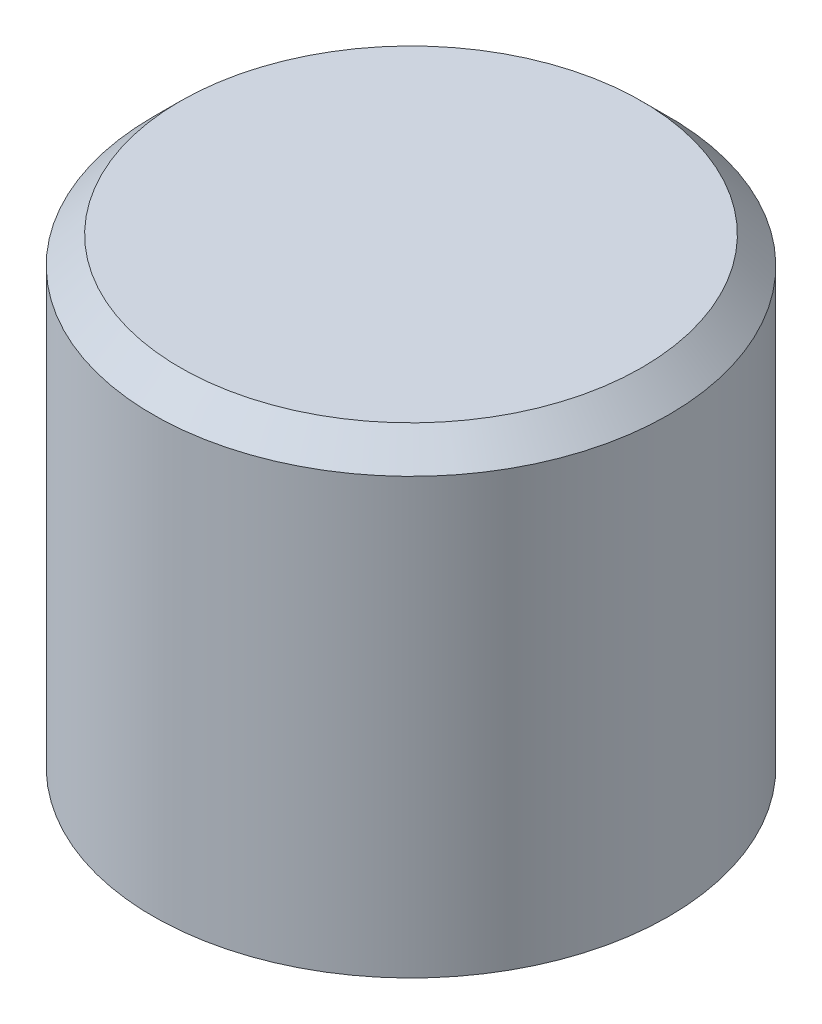
SolidWorks part; units mm, degrees
ref_plane "Front Plane" through (0, 0, 0) normal (0, 0, 1) x (1, 0, 0)
ref_plane "Top Plane" through (0, 0, 0) normal (0, 1, 0) x (1, 0, 0)
ref_plane "Right Plane" through (0, 0, 0) normal (1, 0, 0) x (0, 0, -1)
sketch "Sketch1" plane through (0, 0, 0) normal (0, 0, 1) x (1, 0, 0)
  line L0 (0, 8.5) -> (0, -8.5) construction
  line L1 (0, 8.5) -> (8.5, 8.5)
  line L2 (9.5, 7.5) -> (9.5, -8.5)
  line L3 (9.5, -8.5) -> (8.5, -8.5)
  line L4 (8.5, -8.5) -> (8.5, -3.5)
  line L7 (5.5, -0.5) -> (0, -0.5)
  line L8 (0, -0.5) -> (0, 8.5)
  line L12 (8.5, -3.5) -> (5.5, -0.5)
  line L13 (8.5, 8.5) -> (9.5, 7.5)
  point P3 (0, 0)
  point P5 (9.5, 9.6338)
  point P8 (7.5, 6.5)
  point P9 (4, 6.5)
  point P10 (4, -0.5)
  point P14 (8.5, -0.5)
  point P16 (10.6561, 8.5)
  point P17 (9.5, 8.5)
  dimension "D1" = 17
  dimension "D2" = 9.5
  dimension "D3" = 1
  dimension "D4" = 9
revolve "Revolve1" add sketch "Sketch1" angle 360 about L0
sketch "Sketch2" plane through (0, -0.5, 0) normal (0, -1, 0) x (1, 0, 0)
  circle A1 centre (0, 0) radius 3.175
  dimension "D1" = 6.35
extrude "Cut-Extrude1" cut sketch "Sketch2" against normal offset from surface (7 mm away) 2 up to face at (-8.5, 8.5, 0)
sketch "Sketch3" plane through (0, 0, 0) normal (0, 0, 1) x (1, 0, 0)
  line L1 (8.5, 8.5) -> (-8.5, 8.5) construction
  circle A0 centre (0, 2.5) radius 1.1303
  dimension "D1" = 2.2606
  dimension "D2" = 6
extrude "Cut-Extrude2" cut sketch "Sketch3" against normal up to surface (9.4325 mm away) up to face at (-9.5, 7.5, 0)
